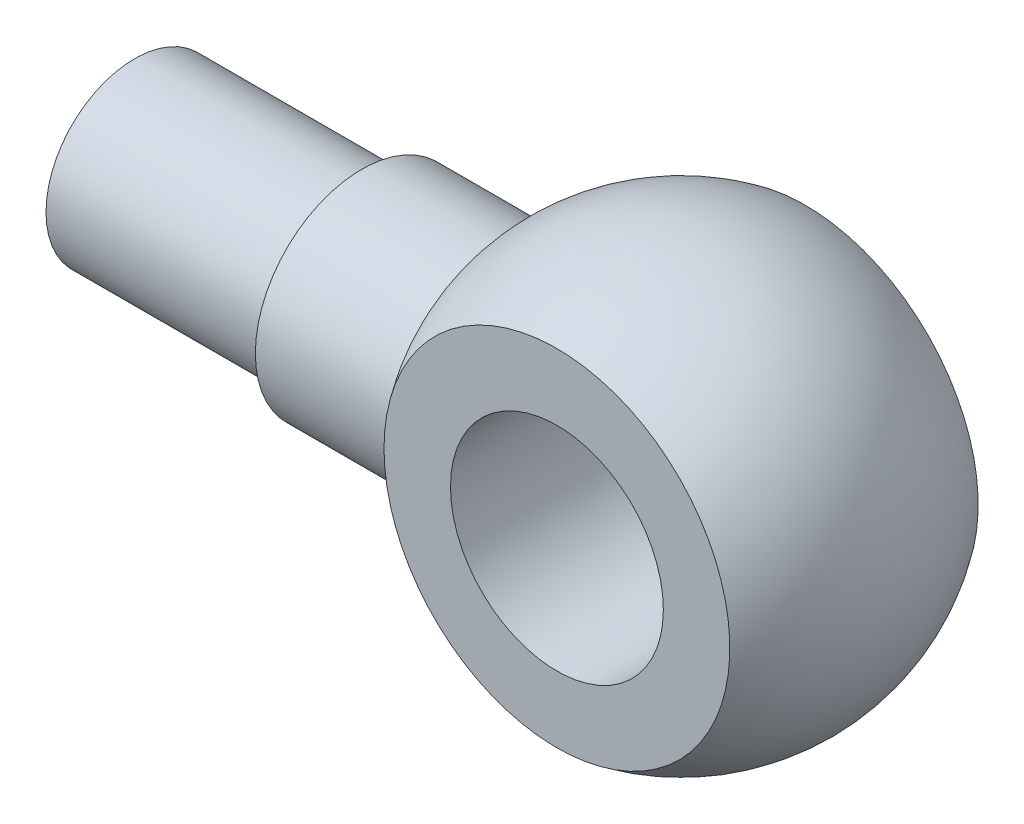
SolidWorks part; units mm, degrees
ref_plane "Přední rovina" through (0, 0, 0) normal (0, 0, 1) x (1, 0, 0)
ref_plane "Vrchní rovina" through (0, 0, 0) normal (0, 1, 0) x (1, 0, 0)
ref_plane "Pravá rovina" through (0, 0, 0) normal (1, 0, 0) x (0, 0, -1)
sketch "Skica1" plane through (0, 0, 0) normal (0, 1, 0) x (1, 0, 0)
  line L0 (-26.2789, 0) -> (118.3581, 0) construction
  line L1 (0, 0) -> (0, 12.5)
  line L2 (0, 12.5) -> (32, 12.5)
  line L3 (32, 12.5) -> (32, 15)
  line L4 (32, 15) -> (51.0192, 15)
  line L5 (92, -17.5) -> (92, 17.5)
  line L6 (92, 17.5) -> (101.367, 17.5)
  line L7 (77, 76.1521) -> (77, -58.3198) construction
  line L8 (62, 17.5) -> (52.633, 17.5) construction
  line L9 (62, 0) -> (62, 17.5) construction
  line L10 (92, -17.5) -> (101.367, -17.5)
  line L11 (51.0192, 15) -> (51.0192, 0)
  line L12 (0, 0) -> (51.0192, 0)
  arc A0 (101.367, 17.5) -> (101.367, -17.5) centre (77, 0) cw
  arc A1 (52.633, 17.5) -> (47, 0) centre (77, 0) ccw construction
  point P14 (213.6375, 0)
  point P17 (-168.9225, 0)
  point P20 (118.3581, 0)
  point P21 (-26.2789, 0)
  point P29 (92, 0)
  dimension "D6" = 35
  dimension "D3" = 30
  dimension "D1" = 32
  dimension "D2" = 45
  dimension "D4" = 25
  dimension "D5" = 30
  dimension "D7" = 30
revolve "Rotovat3" add sketch "Skica1" angle 360 about L0 region at (26.6198, 0, -6.7704)
revolve "Rotovat4" add sketch "Skica1<4>" angle 360 about L7 region at (98.703, 0, 0)
sketch "Skica1<4>" plane through (0, 0, 0) normal (0, 1, 0) x (1, 0, 0) same geometry as "Skica1"
